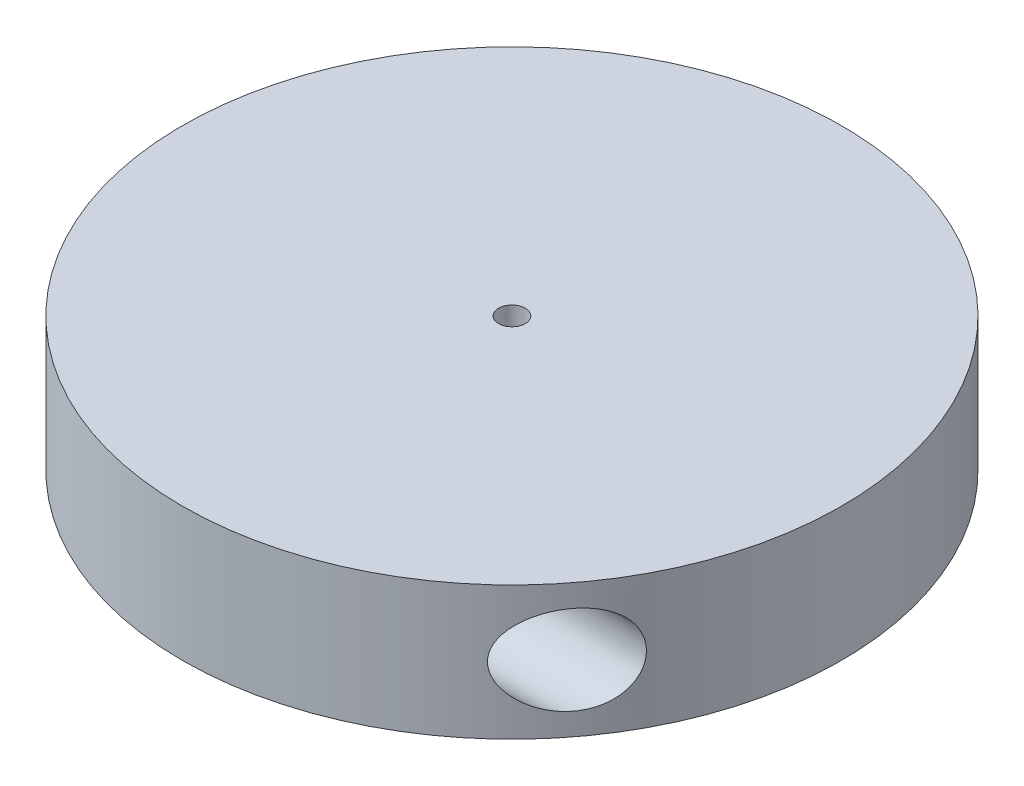
SolidWorks part; units mm, degrees
ref_plane "Front Plane" through (0, 0, 0) normal (0, 0, 1) x (1, 0, 0)
ref_plane "Top Plane" through (0, 0, 0) normal (0, 1, 0) x (1, 0, 0)
ref_plane "Right Plane" through (0, 0, 0) normal (1, 0, 0) x (0, 0, -1)
sketch "Sketch1" plane through (0, 0, 0) normal (0, 1, 0) x (1, 0, 0)
  circle A0 centre (0, 0) radius 74
extrude "Boss-Extrude1" add sketch "Sketch1" along normal blind 30
sketch "Sketch2" plane through (0, 0, 0) normal (1, 0, 0) x (0, 0, -1)
  circle A0 centre (45, 15) radius 10
  point P2 (0, 0)
extrude "Cut-Extrude1" cut sketch "Sketch2" against normal blind 80
sketch "Sketch3" plane through (0, 0, 0) normal (1, 0, 0) x (0, 0, -1)
  circle A0 centre (-45, 15) radius 10
  point P2 (0, 0)
extrude "Cut-Extrude2" cut sketch "Sketch3" along normal blind 80
sketch "Sketch6" plane through (0, 30, 0) normal (0, 1, 0) x (1, 0, 0)
  circle A0 centre (0, 0) radius 3
extrude "Cut-Extrude4" cut sketch "Sketch6" against normal blind 30
